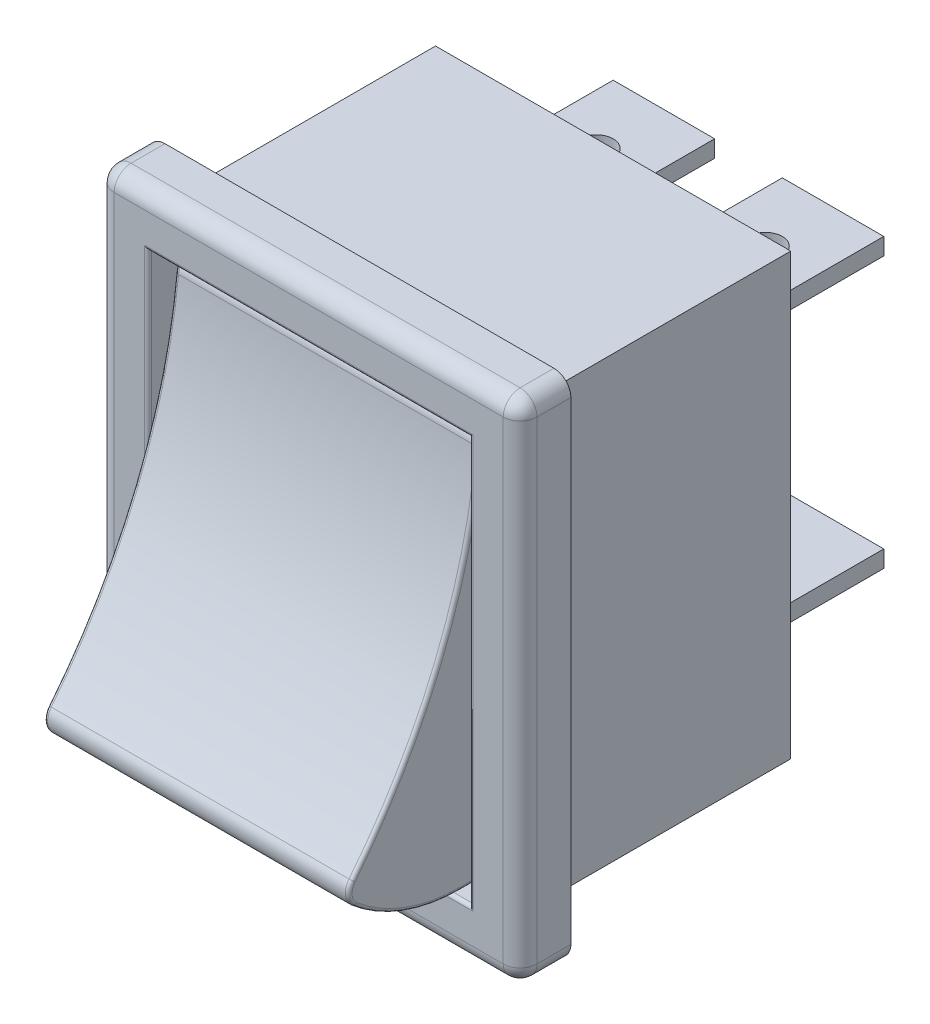
SolidWorks part; units mm, degrees
ref_plane "Plan de face" through (0, 0, 0) normal (0, 0, 1) x (1, 0, 0)
ref_plane "Plan de dessus" through (0, 0, 0) normal (0, 1, 0) x (1, 0, 0)
ref_plane "Plan de droite" through (0, 0, 0) normal (1, 0, 0) x (0, 0, -1)
sketch "Esquisse1" plane through (0, 0, 0) normal (0, 0, 1) x (1, 0, 0)
  line L1 (12.5, -15) -> (-12.5, -15)
  line L2 (12.5, -15) -> (12.5, 15)
  line L3 (12.5, 15) -> (-12.5, 15)
  line L4 (-12.5, -15) -> (-12.5, 15)
  line L5 (12.5, -15) -> (-12.5, 15) construction
  line L6 (12.5, 15) -> (-12.5, -15) construction
  point P0 (0, 0)
  dimension "D1" = 25
  dimension "D2" = 30
extrude "Boss.-Extru.1" add sketch "Esquisse1" along normal blind 3
sketch "Esquisse2" plane through (0, 0, 0) normal (0, 0, -1) x (-1, 0, 0)
  line L0 (-12.5, -15) -> (-12.5, 15) construction
  line L1 (-12.5, 15) -> (12.5, 15) construction
  line L8 (10.5, -13) -> (10.5, 13)
  line L9 (10.5, 13) -> (-10.5, 13)
  line L10 (-10.5, 13) -> (-10.5, -13)
  line L11 (-10.5, -13) -> (10.5, -13)
  line L12 (10.5, -13) -> (10.5, 13)
  line L13 (10.5, 13) -> (-10.5, 13)
  line L14 (-10.5, 13) -> (-10.5, -13)
  line L15 (-10.5, -13) -> (10.5, -13)
  dimension "D1" = 2
extrude "Boss.-Extru.2" add sketch "Esquisse2" along normal blind 15
fillet "Congé1" radius 1 4 edges at (0, 15, 3) (12.5, 0, 3) (0, -15, 3) (-12.5, 0, 3)
fillet "Congé2" radius 1 8 edges at (-12.2071, 14.7071, 2.7071) (-12.2071, -14.7071, 2.7071) (12.2071, -14.7071, 2.7071) (12.2071, 14.7071, 2.7071) (-12.5, 15, 1) (-12.5, -15, 1) (12.5, -15, 1) (12.5, 15, 1)
sketch "Esquisse3" plane through (0, 0, 3) normal (0, 0, 1) x (1, 0, 0)
  line L8 (9.5, -12) -> (9.5, 12)
  line L9 (9.5, 12) -> (-9.5, 12)
  line L10 (-9.5, 12) -> (-9.5, -12)
  line L11 (-9.5, -12) -> (9.5, -12)
  line L12 (9.5, -12) -> (9.5, 12)
  line L13 (9.5, 12) -> (-9.5, 12)
  line L14 (-9.5, 12) -> (-9.5, -12)
  line L15 (-9.5, -12) -> (9.5, -12)
  dimension "D1" = 2
extrude "Enlèv. mat.-Extru.1" cut sketch "Esquisse3" against normal blind 2
fillet "Congé3" radius 0.2 4 edges at (0, -12, 3) (9.5, 0, 3) (0, 12, 3) (-9.5, 0, 3)
sketch "Esquisse5" plane through (0, 0, 0) normal (1, 0, 0) x (0, 0, -1)
  line L0 (-1, 11.5) -> (-1.8159, 11.5)
  line L2 (-3, -11.5) -> (-1, -11.5)
  line L3 (-1, -11.5) -> (-1, 11.5)
  line L4 (-1, 12) -> (-1, -12) construction
  line L5 (15, 13) -> (0, 13) construction
  line L6 (15, -13) -> (0, -13) construction
  arc A0 (-3, -11.5) -> (-10, -8.5) centre (-3, -1.8333) cw
  arc A1 (-10, -8.5) -> (-1.8159, 11.5) centre (-36.7186, 14.1079) ccw
  dimension "D6" = 2
  dimension "D3" = 35
  dimension "D1" = 1.5
  dimension "D2" = 1.5
  dimension "D5" = 9
  dimension "D7" = 20
extrude "Boss.-Extru.4" add sketch "Esquisse5" along normal mid plane 18 separate body contours A0 A1 L0 L3 L2
fillet "Congé6" radius 1 2 edges at (0, 11.5, 1.8159) (0, -8.5, 10)
fillet "Congé7" radius 0.2 12 edges at (-9, -8.5103, 9.6317) (-9, -10.9006, 6.351) (-9, -11.5, 2) (-9, 11.212, 1.6066) (-9, 0.8618, 4.322) (9, -11.5, 2) (9, -10.9006, 6.351) (9, -8.5103, 9.6317) (9, 0.8618, 4.322) (9, 11.212, 1.6066) (-9, 0, 1) (9, 0, 1)
sketch "Esquisse6" plane through (0, 0, -15) normal (0, 0, -1) x (-1, 0, 0)
  line L0 (0, 0) -> (0, 12.0708) construction
  line L1 (-8, 8.5) -> (-2, 8.5)
  line L2 (-8, 8.5) -> (-8, 7.5)
  line L3 (-8, 7.5) -> (-2, 7.5)
  line L4 (-2, 8.5) -> (-2, 7.5)
  line L5 (-8, 8.5) -> (-2, 7.5) construction
  line L6 (-8, 7.5) -> (-2, 8.5) construction
  line L7 (8, 7.5) -> (2, 8.5) construction
  line L8 (8, 8.5) -> (2, 7.5) construction
  line L9 (2, 8.5) -> (2, 7.5)
  line L10 (8, 7.5) -> (2, 7.5)
  line L11 (8, 8.5) -> (8, 7.5)
  line L12 (8, 8.5) -> (2, 8.5)
  line L13 (0.3056, 0) -> (0, 0) construction
  line L14 (0, 0) -> (22.0533, 0) construction
  line L15 (8, -8.5) -> (2, -7.5) construction
  line L16 (8, -7.5) -> (2, -8.5) construction
  line L17 (-8, -7.5) -> (-2, -8.5) construction
  line L18 (-8, -8.5) -> (-2, -7.5) construction
  line L19 (8, -8.5) -> (2, -8.5)
  line L20 (8, -8.5) -> (8, -7.5)
  line L21 (8, -7.5) -> (2, -7.5)
  line L22 (2, -8.5) -> (2, -7.5)
  line L23 (-2, -8.5) -> (-2, -7.5)
  line L24 (-8, -7.5) -> (-2, -7.5)
  line L25 (-8, -8.5) -> (-8, -7.5)
  line L26 (-8, -8.5) -> (-2, -8.5)
  point P0 (-5, 8)
  point P12 (5, 8)
  point P23 (5, -8)
  point P24 (-5, -8)
  dimension "D1" = 6
  dimension "D2" = 1
  dimension "D3" = 5
  dimension "D4" = 8
extrude "Boss.-Extru.5" add sketch "Esquisse6" along normal blind 8
sketch "Esquisse7" plane through (0, 8.5, 0) normal (0, 1, 0) x (1, 0, 0)
  line L0 (2, 23) -> (8, 23) construction
  line L1 (2, 15) -> (8, 15) construction
  line L2 (0, 0) -> (0, 35.5416) construction
  circle A0 centre (5, 19) radius 1
  circle A1 centre (-5, 19) radius 1
  point P5 (5, 23)
  dimension "D1" = 2
  dimension "D2" = 4
extrude "Enlèv. mat.-Extru.2" cut sketch "Esquisse7" against normal through all
sketch "Esquisse8" plane through (0, 0, 0) normal (0, 0, 1) x (1, 0, 0)
  line L0 (-5.0451, 5.4332) -> (5.0451, 5.4332) construction
  line L1 (-5.0451, -7.2632) -> (5.0451, -7.2632) construction
  text T0 "I" font "Century Gothic" height 4.5
  text T1 "O" font "Century Gothic" height 4.5
  point P3 (0, 5.4332)
